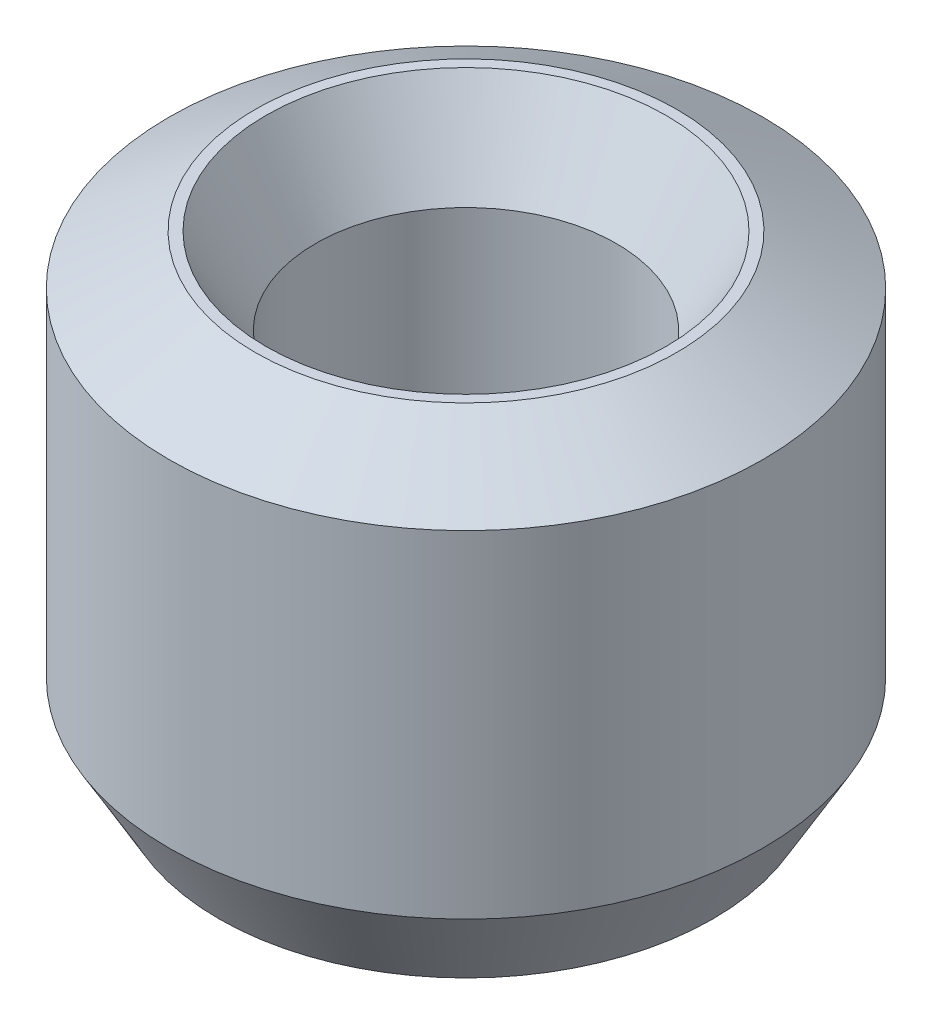
SolidWorks part; units mm, degrees
ref_plane "Front Plane" through (0, 0, 0) normal (0, 0, 1) x (1, 0, 0)
ref_plane "Top Plane" through (0, 0, 0) normal (0, 1, 0) x (1, 0, 0)
ref_plane "Right Plane" through (0, 0, 0) normal (1, 0, 0) x (0, 0, -1)
sketch "Sketch1" plane through (0, 0, 0) normal (0, 1, 0) x (1, 0, 0)
  circle A0 centre (0, 0) radius 20
  dimension "SLEEVE_OD" = 40
extrude "Boss-Extrude1" add sketch "Sketch1" along normal blind 31.8253
sketch "Sketch2" plane through (0, 0, 0) normal (0, 1, 0) x (1, 0, 0)
  circle A0 centre (0, 0) radius 10.1366
  dimension "BORE_D" = 20.2731
extrude "Cut-Extrude1" cut sketch "Sketch2" along normal through all
chamfer "Chamfer1" distance 3.3495 angle 60 4 edges at (0, 31.8253, 10.1366) (0, 0, 10.1366) (0, 0, 20) (0, 31.8253, 20) first distance on face at (0, 31.8253, 10.1366) first distance on face at (0, 0, 10.1366) first distance on face at (0, 31.8253, 20)
